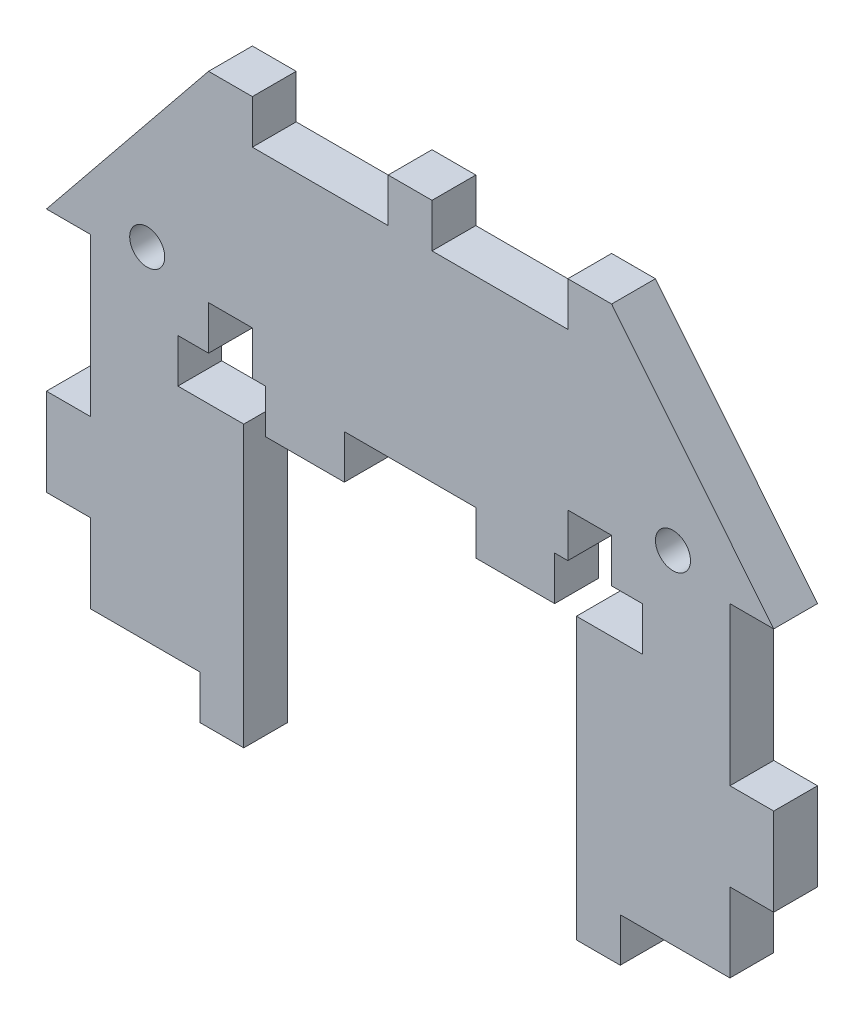
SolidWorks part; units mm, degrees
ref_plane "Plan de face" through (0, 0, 0) normal (0, 0, 1) x (1, 0, 0)
ref_plane "Plan de dessus" through (0, 0, 0) normal (0, 1, 0) x (1, 0, 0)
ref_plane "Plan de droite" through (0, 0, 0) normal (1, 0, 0) x (0, 0, -1)
sketch "Esquisse1" plane through (0, 0, 0) normal (0, 0, 1) x (1, 0, 0)
  line L0 (-23, 0) -> (-41.5, -22.86)
  line L1 (-41.5, -22.86) -> (-41.5, -64.86)
  line L2 (-41.5, -64.86) -> (-18.9833, -64.86)
  line L3 (0, -46.21) -> (0, 0) construction
  line L4 (18.9833, -64.86) -> (18.9833, -32.86)
  line L5 (41.5, -64.86) -> (18.9833, -64.86)
  line L6 (41.5, -22.86) -> (41.5, -64.86)
  line L7 (-23, 0) -> (23, 0)
  line L8 (-18.9833, -32.86) -> (18.9833, -32.86)
  line L9 (-18.9833, -64.86) -> (-18.9833, -32.86)
  line L10 (23, 0) -> (41.5, -22.86)
  dimension "D1" = 46
  dimension "D2" = 22.86
  dimension "D3" = 83
  dimension "D4" = 42
  dimension "D5" = 32
extrude "Boss.-Extru.1" add sketch "Esquisse1" along normal blind 5
sketch "Esquisse2" plane through (0, 0, 5) normal (0, 0, 1) x (1, 0, 0)
  line L0 (41.5, -64.86) -> (41.5, -22.86) construction
  line L1 (36.5, -22.86) -> (41.5, -22.86)
  line L2 (36.5, -22.86) -> (36.5, -40.86)
  line L3 (36.5, -40.86) -> (41.5, -40.86)
  line L4 (41.5, -22.86) -> (41.5, -40.86)
  line L5 (18.9833, -64.86) -> (41.5, -64.86) construction
  line L6 (23.9833, -64.86) -> (41.5, -64.86)
  line L7 (36.5, -50.86) -> (36.5, -59.86)
  line L8 (36.5, -50.86) -> (41.5, -50.86)
  line L9 (41.5, -64.86) -> (41.5, -50.86)
  line L10 (-18, -5) -> (-18, 0) construction
  line L11 (0, 0) -> (0, -59.86) construction
  line L12 (23, 0) -> (-23, 0) construction
  line L13 (-41.5, -64.86) -> (-41.5, -50.86)
  line L14 (-36.5, -50.86) -> (-41.5, -50.86)
  line L15 (-23.9833, -64.86) -> (-41.5, -64.86)
  line L16 (-23.9833, -59.86) -> (-23.9833, -64.86)
  line L17 (-41.5, -22.86) -> (-41.5, -40.86)
  line L18 (-36.5, -40.86) -> (-41.5, -40.86)
  line L19 (-36.5, -22.86) -> (-36.5, -40.86)
  line L20 (-36.5, -22.86) -> (-41.5, -22.86)
  line L21 (36.5, -59.86) -> (23.9833, -59.86)
  line L22 (23.9833, -59.86) -> (23.9833, -64.86)
  line L23 (18.9833, -64.86) -> (41.5, -64.86) construction
  line L24 (23.9833, -59.86) -> (23.9833, -64.86) construction
  line L25 (-36.5, -50.86) -> (-36.5, -59.86)
  line L26 (-36.5, -59.86) -> (-23.9833, -59.86)
  line L27 (-18.9833, -32.86) -> (18.9833, -32.86) construction
  line L28 (-26.5, -27.86) -> (-16.5, -27.86)
  line L29 (-26.5, -27.86) -> (-26.5, -32.86)
  line L30 (-26.5, -32.86) -> (-16.5, -32.86)
  line L31 (-16.5, -27.86) -> (-16.5, -32.86)
  line L32 (-7.5, -27.86) -> (-7.5, -32.86)
  line L33 (-18, 0) -> (-2.5, 0)
  line L34 (7.5, -27.86) -> (7.5, -32.86)
  line L35 (16.5, -27.86) -> (16.5, -32.86)
  line L36 (26.5, -32.86) -> (16.5, -32.86)
  line L37 (26.5, -27.86) -> (26.5, -32.86)
  line L38 (26.5, -27.86) -> (16.5, -27.86)
  line L39 (-7.5, -27.86) -> (7.5, -27.86)
  line L40 (7.5, -32.86) -> (-7.5, -32.86)
  line L41 (-18, 0) -> (-18, -5)
  line L42 (-18, -5) -> (-2.5, -5)
  line L43 (-2.5, 0) -> (-2.5, -5)
  line L44 (2.5, 0) -> (2.5, -5)
  line L45 (18, -5) -> (2.5, -5)
  line L46 (18, 0) -> (18, -5)
  line L47 (18, 0) -> (2.5, 0)
  dimension "D1" = 10
  dimension "D2" = 14
  dimension "D3" = 5
  dimension "D4" = 10
extrude "Enlèv. mat.-Extru.1" cut sketch "Esquisse2" against normal blind 5
sketch "Esquisse3" plane through (0, 0, 5) normal (0, 0, 1) x (1, 0, 0)
  line L0 (26.5, -27.86) -> (16.5, -27.86) construction
  line L1 (18, -22.86) -> (23, -22.86)
  line L2 (18, -22.86) -> (18, -27.86)
  line L3 (18, -27.86) -> (23, -27.86)
  line L4 (23, -22.86) -> (23, -27.86)
  line L5 (23, -22.86) -> (23, -27.86) construction
  line L6 (0, 0) -> (0, -27.86) construction
  line L7 (7.5, -27.86) -> (-7.5, -27.86) construction
  line L8 (-23, -22.86) -> (-23, -27.86)
  line L9 (-18, -27.86) -> (-23, -27.86)
  line L10 (-18, -22.86) -> (-18, -27.86)
  line L11 (-18, -22.86) -> (-23, -22.86)
extrude "Enlèv. mat.-Extru.2" cut sketch "Esquisse3" against normal blind 5
hole_wizard "Trous de centrage Ø4.0mm4" positions "Esquisse10" profile "Esquisse11" hole size "Ø4.0" standard "Ansi Metric" end condition through all
sketch "Esquisse10" plane through (42.8876, 88.2204, -73) normal (0, 0, -1) x (0.866, -0.5, 0)
  point P0 (65.7012, -88.0226)
  point P3 (117.6627, -58.0226)
  point P6 (-109.0804, -72.8876)
  point P9 (-109.0804, -12.8876)
  point P12 (-8.5823, 130.9102)
  point P15 (43.3792, 100.9102)
sketch "Esquisse11" plane through (143.7978, 131.5996, -73) normal (1, 0, 0) x (0, 1, 0)
  line L0 (0, 0) -> (0, 78)
  line L1 (0, 78) -> (2, 78)
  line L2 (2, 78) -> (2, 0)
  line L3 (2, 0) -> (0, 0)
  line L4 (0, -6.35) -> (0, 107.95) construction
  dimension "Diamètre du perçage jusqu'au prochain" = 4
  dimension "Profondeur du perçage jusqu'au prochain" = 78
hole_wizard "Trous de centrage Ø4.0mm5" positions "Esquisse12" profile "Esquisse13" hole size "Ø4.0" standard "Ansi Metric" end condition through all
sketch "Esquisse12" plane through (42.8876, 88.2204, -73) normal (0, 0, -1) x (0, 1, 0)
  point P0 (65.7012, -88.0226)
  point P3 (117.6627, -58.0226)
  point P6 (-109.0804, -72.8876)
  point P9 (-109.0804, -12.8876)
  point P12 (-8.5823, 130.9102)
  point P15 (43.3792, 100.9102)
sketch "Esquisse13" plane through (-45.135, 153.9216, -73) normal (1, 0, 0) x (0, 1, 0)
  line L0 (0, 0) -> (0, 78)
  line L1 (0, 78) -> (2, 78)
  line L2 (2, 78) -> (2, 0)
  line L3 (2, 0) -> (0, 0)
  line L4 (0, -6.35) -> (0, 107.95) construction
  dimension "Diamètre du perçage jusqu'au prochain" = 4
  dimension "Profondeur du perçage jusqu'au prochain" = 78
hole_wizard "Trous de centrage Ø4.0mm6" positions "Esquisse14" profile "Esquisse15" hole size "Ø4.0" standard "Ansi Metric" end condition through all
sketch "Esquisse14" plane through (42.8876, 88.2204, -73) normal (0, 0, -1) x (-0.866, -0.5, 0)
  point P0 (65.7012, -88.0226)
  point P3 (117.6627, -58.0226)
  point P6 (-109.0804, -72.8876)
  point P9 (-109.0804, -12.8876)
  point P12 (-8.5823, 130.9102)
  point P15 (43.3792, 100.9102)
sketch "Esquisse15" plane through (30, -20.86, -73) normal (1, 0, 0) x (0, 1, 0)
  line L0 (0, 0) -> (0, 78)
  line L1 (0, 78) -> (2, 78)
  line L2 (2, 78) -> (2, 0)
  line L3 (2, 0) -> (0, 0)
  line L4 (0, -6.35) -> (0, 107.95) construction
  dimension "Diamètre du perçage jusqu'au prochain" = 4
  dimension "Profondeur du perçage jusqu'au prochain" = 78
